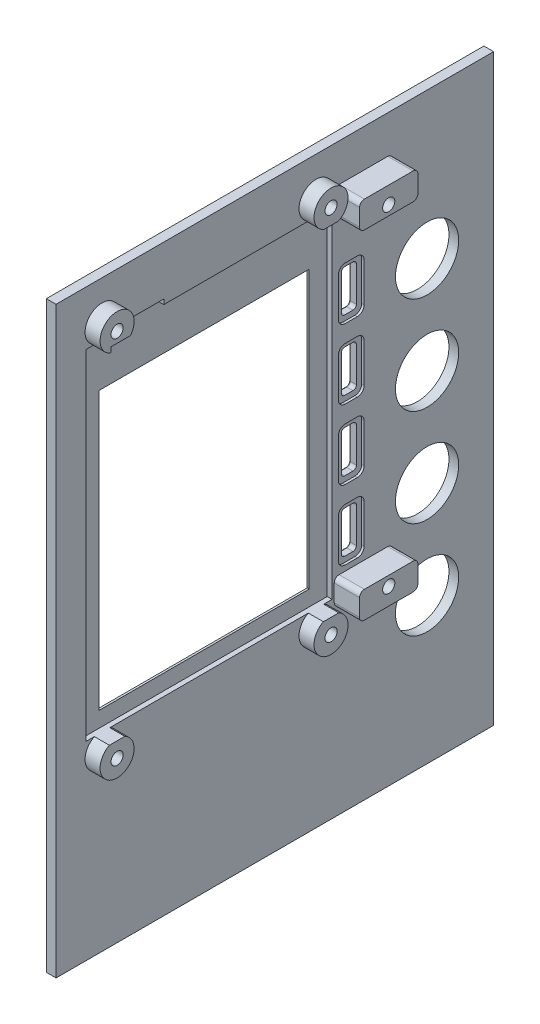
SolidWorks part; units mm, degrees
ref_plane "Front Plane" through (0, 0, 0) normal (0, 0, 1) x (1, 0, 0)
ref_plane "Top Plane" through (0, 0, 0) normal (0, 1, 0) x (1, 0, 0)
ref_plane "Right Plane" through (0, 0, 0) normal (1, 0, 0) x (0, 0, -1)
ref_plane "Plane2" through (-1175.0441, 0, 0) normal (-1, 0, 0) x (0, 0, 1)
sketch "Sketch2" plane through (-1175.0441, 0, 0) normal (-1, 0, 0) x (0, 0, 1)
  line L0 (-1293.9703, -887.0459) -> (-1293.9703, -787.0459) construction
  line L1 (-1208.9703, -777.0459) -> (-1298.9703, -777.0459)
  line L2 (-1208.9703, -777.0459) -> (-1208.9703, -897.0459)
  line L3 (-1208.9703, -897.0459) -> (-1298.9703, -897.0459)
  line L4 (-1298.9703, -777.0459) -> (-1298.9703, -897.0459)
  line L5 (-1293.9703, -887.0459) -> (-1292.4603, -887.0459) construction
  line L6 (-1293.9703, -787.0459) -> (-1292.4603, -787.0459) construction
  circle A0 centre (-1285.2753, -867.0459) radius 6.5
  circle A1 centre (-1285.2753, -847.0459) radius 6.5
  circle A2 centre (-1285.2753, -827.0459) radius 6.5
  circle A3 centre (-1285.2753, -807.0459) radius 6.5
  ellipse E0 centre (-1285.2753, -867.0459) end of major axis (-1284.8157, -867.5055) minor radius 0.65 construction
  ellipse E1 centre (-1285.2753, -847.0459) end of major axis (-1284.8157, -847.5055) minor radius 0.65 construction
  ellipse E2 centre (-1285.2753, -827.0459) end of major axis (-1284.8157, -827.5055) minor radius 0.65 construction
  ellipse E3 centre (-1285.2753, -807.0459) end of major axis (-1284.8157, -807.5055) minor radius 0.65 construction
  ellipse E4 centre (-1285.2753, -867.0459) end of major axis (-1284.8157, -867.5055) minor radius 0.65
  ellipse E5 centre (-1285.2753, -847.0459) end of major axis (-1284.8157, -847.5055) minor radius 0.65 construction
  ellipse E6 centre (-1285.2753, -827.0459) end of major axis (-1284.8157, -827.5055) minor radius 0.65
  ellipse E7 centre (-1285.2753, -807.0459) end of major axis (-1284.8157, -807.5055) minor radius 0.65
  dimension "D5" = 13
  dimension "D6" = 13
  dimension "D7" = 13
  dimension "D8" = 13
  dimension "D1" = 5
  dimension "D2" = 10
  dimension "D3" = 10
  dimension "D4" = 90
extrude "Boss-Extrude2" add sketch "Sketch2" along normal blind 2 contours L1 L4 L3 L2 A3 A2 A1 A0 region at (-1175.0441, -837.0459, -1252.3518)
sketch "Sketch3" plane through (-1177.0441, 0, 0) normal (-1, 0, 0) x (0, 0, 1)
  line L12 (-1218.8332, -854.8056) -> (-1262.0332, -854.8056) construction
  line L13 (-1262.0332, -854.8056) -> (-1262.0332, -797.8256) construction
  line L14 (-1218.8332, -797.8256) -> (-1218.8332, -854.8056) construction
  line L15 (-1262.0332, -797.8256) -> (-1218.8332, -797.8256) construction
  line L16 (-1218.8332, -854.8056) -> (-1262.0332, -854.8056)
  line L17 (-1262.0332, -854.8056) -> (-1262.0332, -797.8256)
  line L18 (-1218.8332, -797.8256) -> (-1218.8332, -854.8056)
  line L19 (-1262.0332, -797.8256) -> (-1218.8332, -797.8256)
extrude "tft_cutout" cut sketch "Sketch3" against normal through all
sketch "tft_inset_cutout" plane through (-1175.0441, 0, 0) normal (1, 0, 0) x (0, 0, -1)
  line L4 (1215.6332, -788.6846) -> (1215.6332, -857.4846) construction
  line L5 (1265.2332, -788.6846) -> (1215.6332, -788.6846) construction
  line L12 (1265.2332, -857.4846) -> (1265.2332, -788.6846) construction
  line L17 (1215.6332, -857.4846) -> (1265.2332, -857.4846) construction
  line L18 (1265.2332, -857.4846) -> (1265.2332, -788.6846) construction
  line L19 (1215.6332, -857.4846) -> (1265.2332, -857.4846) construction
  line L20 (1215.6332, -788.6846) -> (1215.6332, -857.4846) construction
  line L21 (1265.2332, -788.6846) -> (1215.6332, -788.6846) construction
  line L22 (1265.7332, -788.1846) -> (1215.1332, -788.1846)
  line L26 (1217.1332, -788.6846) -> (1231.1332, -788.6846)
  line L27 (1217.1332, -788.6846) -> (1217.1332, -787.1846)
  line L28 (1217.1332, -787.1846) -> (1231.1332, -787.1846)
  line L29 (1231.1332, -788.6846) -> (1231.1332, -787.1846)
  line L30 (1215.1332, -788.1846) -> (1215.1332, -857.9846)
  line L31 (1215.1332, -857.9846) -> (1265.7332, -857.9846)
  line L32 (1265.7332, -857.9846) -> (1265.7332, -788.1846)
  line M40 (1262.0332, -854.8056) -> (1218.8332, -854.8056)
  line M41 (1218.8332, -854.8056) -> (1218.8332, -797.8256)
  line M42 (1218.8332, -797.8256) -> (1262.0332, -797.8256)
  line M43 (1262.0332, -797.8256) -> (1262.0332, -854.8056)
  dimension "D3" = 1.5
  dimension "D4" = 0.5
  dimension "D1" = 14
  dimension "D2" = 1.5
extrude "Cut-Extrude2" cut sketch "tft_inset_cutout" against normal up to surface (1 mm away) contours L18 | L31 L32 L22 L29 L26 L27 L30 M43 M40 M41 M42 | L26 L29 L22 L27 | L22 L29 L28 L27 region at (-1175.0441, -823.0846, -1264.8711) region at (-1175.0441, -788.4346, -1224.1332) region at (-1175.0441, -787.6846, -1224.1332)
chamfer "Chamfer2" distance 1 angle 30 4 edges at (-1177.0441, -826.3156, -1262.0332) (-1177.0441, -854.8056, -1240.4332) (-1177.0441, -826.3156, -1218.8332) (-1177.0441, -797.8256, -1240.4332) first distance on face at (-1177.0441, -826.3156, -1240.4332)
sketch "Sketch6" plane through (-1175.0441, 0, 0) normal (1, 0, 0) x (0, 0, -1)
  line L5 (1266.1832, -859.8139) -> (1278.1832, -859.8139)
  line L6 (1266.1832, -859.8139) -> (1266.1832, -854.3139)
  line L7 (1266.1832, -854.3139) -> (1278.1832, -854.3139)
  line L8 (1266.1832, -859.8139) -> (1278.1832, -859.8139)
  line L9 (1278.1832, -859.8139) -> (1278.1832, -784.8139)
  line L10 (1278.1832, -784.8139) -> (1266.1832, -784.8139)
  line L11 (1266.1832, -784.8139) -> (1266.1832, -859.8139)
  line L12 (1266.1832, -859.8139) -> (1278.1832, -859.8139) construction
  line L13 (1278.1832, -859.8139) -> (1278.1832, -784.8139) construction
  line L14 (1278.1832, -784.8139) -> (1266.1832, -784.8139) construction
  line L15 (1266.1832, -784.8139) -> (1266.1832, -859.8139) construction
  line L16 (1278.1832, -859.8139) -> (1278.1832, -854.3139)
  line L17 (1266.1832, -784.8139) -> (1278.1832, -784.8139)
  line L18 (1266.1832, -784.8139) -> (1266.1832, -790.3139)
  line L19 (1266.1832, -790.3139) -> (1278.1832, -790.3139)
  line L20 (1278.1832, -784.8139) -> (1278.1832, -790.3139)
  circle A0 centre (1272.1832, -856.3139) radius 1.25 construction
  circle A1 centre (1272.1832, -856.3139) radius 1.25 construction
  circle A2 centre (1272.1832, -856.3139) radius 1.25
  circle A3 centre (1272.1832, -788.3139) radius 1.25 construction
  circle A4 centre (1272.1832, -788.3139) radius 1.25 construction
  circle A5 centre (1272.1832, -788.3139) radius 1.25
  dimension "D2" = 2.5
  dimension "D4" = 2.5
  dimension "D3" = 2
  dimension "D5" = 2
extrude "menu_standoffs" add sketch "Sketch6" along normal up to surface (5.203 mm away)
fillet "Fillet1" radius 1 8 edges at (-1172.4426, -790.3139, -1266.1832) (-1172.4426, -790.3139, -1278.1832) (-1172.4426, -784.8139, -1278.1832) (-1172.4426, -784.8139, -1266.1832) (-1172.4426, -854.3139, -1278.1832) (-1172.4426, -854.3139, -1266.1832) (-1172.4426, -859.8139, -1266.1832) (-1172.4426, -859.8139, -1278.1832)
sketch "Sketch7" plane through (-1169.8411, 0, 0) normal (1, 0, 0) x (0, 0, -1)
  circle A0 centre (1272.1832, -856.3139) radius 1.25 construction
  circle A1 centre (1272.1832, -788.3139) radius 1.25 construction
  circle A2 centre (1272.1832, -856.3139) radius 1.25
  circle A3 centre (1272.1832, -788.3139) radius 1.25
extrude "menu_standoff_holes" [suppressed] cut sketch "Sketch7" against normal blind 5 contours A2
sketch "Sketch8" plane through (-1175.0441, 0, 0) normal (1, 0, 0) x (0, 0, -1)
  circle A0 centre (1218.4332, -861.1056) radius 1.55 construction
  circle A1 centre (1262.4332, -861.1056) radius 1.55 construction
  circle A2 centre (1262.4332, -785.0256) radius 1.55 construction
  circle A3 centre (1218.4332, -785.0258) radius 1.55 construction
  circle A4 centre (1218.4332, -861.1056) radius 1.55 construction
  circle A5 centre (1262.4332, -861.1056) radius 1.55 construction
  circle A6 centre (1262.4332, -785.0256) radius 1.55 construction
  circle A7 centre (1218.4332, -785.0258) radius 1.55 construction
  circle A8 centre (1218.4332, -785.0258) radius 3.5
  circle A9 centre (1262.4332, -785.0256) radius 3.5
  circle A10 centre (1262.4332, -861.1056) radius 3.5
  circle A11 centre (1218.4332, -861.1056) radius 3.5
  circle A12 centre (1218.4332, -785.0258) radius 1.25
  circle A13 centre (1218.4332, -861.1056) radius 1.25
  circle A14 centre (1262.4332, -861.1056) radius 1.25
  circle A15 centre (1262.4332, -785.0256) radius 1.25
  dimension "D2" = 2.5
  dimension "D1" = 7
extrude "TFT_standoffs" add sketch "Sketch8" along normal up to surface (3.09 mm away)
sketch "Sketch9" plane through (-1175.0441, 0, 0) normal (1, 0, 0) x (0, 0, -1)
  circle A0 centre (1218.4332, -785.0258) radius 1.25 construction
  circle A1 centre (1218.4332, -861.1056) radius 1.25 construction
  circle A2 centre (1262.4332, -861.1056) radius 1.25 construction
  circle A3 centre (1262.4332, -785.0256) radius 1.25 construction
  circle A4 centre (1218.4332, -785.0258) radius 1.25
  circle A5 centre (1218.4332, -861.1056) radius 1.25
  circle A6 centre (1262.4332, -861.1056) radius 1.25
  circle A7 centre (1262.4332, -785.0256) radius 1.25
extrude "TFT_standoff_holes" cut sketch "Sketch9" against normal offset from surface (1 mm away) 1 up to face at (-1177.0441, -826.3156, -1240.4332)
extrude "Cut-Extrude5" cut sketch "Sketch5<3>" along normal through all contours L31 L32 L22 L29 L26 L27 L30 M43 M40 M41 M42 | L22 L29 L28 L27 | L26 L29 L22 L27 region at (-1175.0441, -823.0846, -1264.8711) region at (-1175.0441, -788.4346, -1224.1332) region at (-1175.0441, -787.6846, -1224.1332)
sketch "Sketch5<3>" plane through (-1175.0441, 0, 0) normal (1, 0, 0) x (0, 0, -1) same geometry as "tft_inset_cutout"
sketch "Sketch10" plane through (-1175.0441, 0, 0) normal (1, 0, 0) x (0, 0, -1)
  line L0 (1271.9367, -800.8206) -> (1271.9367, -808.8206) construction
  line L1 (1270.9367, -809.8206) -> (1268.4367, -809.8206) construction
  line L2 (1267.4367, -808.8206) -> (1267.4367, -800.8206) construction
  line L3 (1268.4367, -799.8206) -> (1270.9367, -799.8206) construction
  line L4 (1271.9367, -800.8206) -> (1271.9367, -808.8206) construction
  line L5 (1270.9367, -809.8206) -> (1268.4367, -809.8206) construction
  line L6 (1267.4367, -808.8206) -> (1267.4367, -800.8206) construction
  line L7 (1268.4367, -799.8206) -> (1270.9367, -799.8206) construction
  line L8 (1272.3367, -800.8206) -> (1272.3367, -808.8206)
  line L9 (1270.9367, -810.2206) -> (1268.4367, -810.2206)
  line L10 (1267.0367, -808.8206) -> (1267.0367, -800.8206)
  line L11 (1268.4367, -799.4206) -> (1270.9367, -799.4206)
  line L12 (1272.3367, -815.1506) -> (1272.3367, -823.1506)
  line L13 (1270.9367, -824.5506) -> (1268.4367, -824.5506)
  line L14 (1267.0367, -823.1506) -> (1267.0367, -815.1506)
  line L15 (1268.4367, -813.7506) -> (1270.9367, -813.7506)
  line L16 (1271.9367, -815.1506) -> (1271.9367, -823.1506) construction
  line L17 (1270.9367, -824.1506) -> (1268.4367, -824.1506) construction
  line L18 (1267.4367, -823.1506) -> (1267.4367, -815.1506) construction
  line L19 (1268.4367, -814.1506) -> (1270.9367, -814.1506) construction
  line L20 (1272.3367, -829.4806) -> (1272.3367, -837.4806)
  line L21 (1270.9367, -838.8806) -> (1268.4367, -838.8806)
  line L22 (1267.0367, -837.4806) -> (1267.0367, -829.4806)
  line L23 (1268.4367, -828.0806) -> (1270.9367, -828.0806)
  line L24 (1271.9367, -829.4806) -> (1271.9367, -837.4806) construction
  line L25 (1270.9367, -838.4806) -> (1268.4367, -838.4806) construction
  line L26 (1267.4367, -837.4806) -> (1267.4367, -829.4806) construction
  line L27 (1268.4367, -828.4806) -> (1270.9367, -828.4806) construction
  line L28 (1272.3367, -843.8106) -> (1272.3367, -851.8106)
  line L29 (1270.9367, -853.2106) -> (1268.4367, -853.2106)
  line L30 (1267.0367, -851.8106) -> (1267.0367, -843.8106)
  line L31 (1268.4367, -842.4106) -> (1270.9367, -842.4106)
  line L32 (1271.9367, -843.8106) -> (1271.9367, -851.8106) construction
  line L33 (1270.9367, -852.8106) -> (1268.4367, -852.8106) construction
  line L34 (1267.4367, -851.8106) -> (1267.4367, -843.8106) construction
  line L35 (1268.4367, -842.8106) -> (1270.9367, -842.8106) construction
  arc A0 (1271.9367, -800.8206) -> (1270.9367, -799.8206) centre (1270.9367, -800.8206) ccw construction
  arc A1 (1270.9367, -809.8206) -> (1271.9367, -808.8206) centre (1270.9367, -808.8206) ccw construction
  arc A2 (1267.4367, -808.8206) -> (1268.4367, -809.8206) centre (1268.4367, -808.8206) ccw construction
  arc A3 (1268.4367, -799.8206) -> (1267.4367, -800.8206) centre (1268.4367, -800.8206) ccw construction
  arc A4 (1271.9367, -800.8206) -> (1270.9367, -799.8206) centre (1270.9367, -800.8206) ccw construction
  arc A5 (1270.9367, -809.8206) -> (1271.9367, -808.8206) centre (1270.9367, -808.8206) ccw construction
  arc A6 (1267.4367, -808.8206) -> (1268.4367, -809.8206) centre (1268.4367, -808.8206) ccw construction
  arc A7 (1268.4367, -799.8206) -> (1267.4367, -800.8206) centre (1268.4367, -800.8206) ccw construction
  arc A8 (1270.9367, -810.2206) -> (1272.3367, -808.8206) centre (1270.9367, -808.8206) ccw
  arc A9 (1267.0367, -808.8206) -> (1268.4367, -810.2206) centre (1268.4367, -808.8206) ccw
  arc A10 (1268.4367, -799.4206) -> (1267.0367, -800.8206) centre (1268.4367, -800.8206) ccw
  arc A11 (1272.3367, -800.8206) -> (1270.9367, -799.4206) centre (1270.9367, -800.8206) ccw
  arc A12 (1270.9367, -824.5506) -> (1272.3367, -823.1506) centre (1270.9367, -823.1506) ccw
  arc A13 (1267.0367, -823.1506) -> (1268.4367, -824.5506) centre (1268.4367, -823.1506) ccw
  arc A14 (1268.4367, -813.7506) -> (1267.0367, -815.1506) centre (1268.4367, -815.1506) ccw
  arc A15 (1272.3367, -815.1506) -> (1270.9367, -813.7506) centre (1270.9367, -815.1506) ccw
  arc A16 (1271.9367, -815.1506) -> (1270.9367, -814.1506) centre (1270.9367, -815.1506) ccw construction
  arc A17 (1270.9367, -824.1506) -> (1271.9367, -823.1506) centre (1270.9367, -823.1506) ccw construction
  arc A18 (1267.4367, -823.1506) -> (1268.4367, -824.1506) centre (1268.4367, -823.1506) ccw construction
  arc A19 (1268.4367, -814.1506) -> (1267.4367, -815.1506) centre (1268.4367, -815.1506) ccw construction
  arc A20 (1270.9367, -838.8806) -> (1272.3367, -837.4806) centre (1270.9367, -837.4806) ccw
  arc A21 (1267.0367, -837.4806) -> (1268.4367, -838.8806) centre (1268.4367, -837.4806) ccw
  arc A22 (1268.4367, -828.0806) -> (1267.0367, -829.4806) centre (1268.4367, -829.4806) ccw
  arc A23 (1272.3367, -829.4806) -> (1270.9367, -828.0806) centre (1270.9367, -829.4806) ccw
  arc A24 (1271.9367, -829.4806) -> (1270.9367, -828.4806) centre (1270.9367, -829.4806) ccw construction
  arc A25 (1270.9367, -838.4806) -> (1271.9367, -837.4806) centre (1270.9367, -837.4806) ccw construction
  arc A26 (1267.4367, -837.4806) -> (1268.4367, -838.4806) centre (1268.4367, -837.4806) ccw construction
  arc A27 (1268.4367, -828.4806) -> (1267.4367, -829.4806) centre (1268.4367, -829.4806) ccw construction
  arc A28 (1270.9367, -853.2106) -> (1272.3367, -851.8106) centre (1270.9367, -851.8106) ccw
  arc A29 (1267.0367, -851.8106) -> (1268.4367, -853.2106) centre (1268.4367, -851.8106) ccw
  arc A30 (1268.4367, -842.4106) -> (1267.0367, -843.8106) centre (1268.4367, -843.8106) ccw
  arc A31 (1272.3367, -843.8106) -> (1270.9367, -842.4106) centre (1270.9367, -843.8106) ccw
  arc A32 (1271.9367, -843.8106) -> (1270.9367, -842.8106) centre (1270.9367, -843.8106) ccw construction
  arc A33 (1270.9367, -852.8106) -> (1271.9367, -851.8106) centre (1270.9367, -851.8106) ccw construction
  arc A34 (1267.4367, -851.8106) -> (1268.4367, -852.8106) centre (1268.4367, -851.8106) ccw construction
  arc A35 (1268.4367, -842.8106) -> (1267.4367, -843.8106) centre (1268.4367, -843.8106) ccw construction
  dimension "D1" = 0.4
  dimension "D2" = 4
extrude "Cut-Extrude6" cut sketch "Sketch10" against normal offset from surface 1.5 and the other way through all up to face at (-1177.0441, -826.3156, -1240.4332)
sketch "Sketch11" plane through (-1177.0441, 0, 0) normal (-1, 0, 0) x (0, 0, 1)
  line L0 (-1270.5367, -808.8206) -> (-1268.8367, -808.8206) construction
  line L1 (-1270.9367, -801.2206) -> (-1270.9367, -808.4206) construction
  line L2 (-1270.5367, -800.8206) -> (-1268.8367, -800.8206) construction
  line L3 (-1268.4367, -801.2206) -> (-1268.4367, -808.4206) construction
  line L4 (-1270.5367, -808.8206) -> (-1268.8367, -808.8206) construction
  line L5 (-1270.9367, -801.2206) -> (-1270.9367, -808.4206) construction
  line L6 (-1270.5367, -800.8206) -> (-1268.8367, -800.8206) construction
  line L7 (-1268.4367, -801.2206) -> (-1268.4367, -808.4206) construction
  line L8 (-1268.1367, -801.2206) -> (-1268.1367, -808.4206)
  line L9 (-1270.5367, -809.1206) -> (-1268.8367, -809.1206)
  line L10 (-1271.2367, -801.2206) -> (-1271.2367, -808.4206)
  line L11 (-1270.5367, -800.5206) -> (-1268.8367, -800.5206)
  line L12 (-1268.1367, -815.5506) -> (-1268.1367, -822.7506)
  line L13 (-1270.5367, -823.4506) -> (-1268.8367, -823.4506)
  line L14 (-1271.2367, -815.5506) -> (-1271.2367, -822.7506)
  line L15 (-1270.5367, -814.8506) -> (-1268.8367, -814.8506)
  line L16 (-1270.5367, -823.1506) -> (-1268.8367, -823.1506) construction
  line L17 (-1270.9367, -815.5506) -> (-1270.9367, -822.7506) construction
  line L18 (-1270.5367, -815.1506) -> (-1268.8367, -815.1506) construction
  line L19 (-1268.4367, -815.5506) -> (-1268.4367, -822.7506) construction
  line L20 (-1268.1367, -829.8806) -> (-1268.1367, -837.0806)
  line L21 (-1270.5367, -837.7806) -> (-1268.8367, -837.7806)
  line L22 (-1271.2367, -829.8806) -> (-1271.2367, -837.0806)
  line L23 (-1270.5367, -829.1806) -> (-1268.8367, -829.1806)
  line L24 (-1270.5367, -837.4806) -> (-1268.8367, -837.4806) construction
  line L25 (-1270.9367, -829.8806) -> (-1270.9367, -837.0806) construction
  line L26 (-1270.5367, -829.4806) -> (-1268.8367, -829.4806) construction
  line L27 (-1268.4367, -829.8806) -> (-1268.4367, -837.0806) construction
  line L28 (-1268.1367, -844.2106) -> (-1268.1367, -851.4106)
  line L29 (-1270.5367, -852.1106) -> (-1268.8367, -852.1106)
  line L30 (-1271.2367, -844.2106) -> (-1271.2367, -851.4106)
  line L31 (-1270.5367, -843.5106) -> (-1268.8367, -843.5106)
  line L32 (-1270.5367, -851.8106) -> (-1268.8367, -851.8106) construction
  line L33 (-1270.9367, -844.2106) -> (-1270.9367, -851.4106) construction
  line L34 (-1270.5367, -843.8106) -> (-1268.8367, -843.8106) construction
  line L35 (-1268.4367, -844.2106) -> (-1268.4367, -851.4106) construction
  arc A0 (-1268.8367, -808.8206) -> (-1268.4367, -808.4206) centre (-1268.8367, -808.4206) ccw construction
  arc A1 (-1270.9367, -808.4206) -> (-1270.5367, -808.8206) centre (-1270.5367, -808.4206) ccw construction
  arc A2 (-1270.5367, -800.8206) -> (-1270.9367, -801.2206) centre (-1270.5367, -801.2206) ccw construction
  arc A3 (-1268.4367, -801.2206) -> (-1268.8367, -800.8206) centre (-1268.8367, -801.2206) ccw construction
  arc A4 (-1268.8367, -808.8206) -> (-1268.4367, -808.4206) centre (-1268.8367, -808.4206) ccw construction
  arc A5 (-1270.9367, -808.4206) -> (-1270.5367, -808.8206) centre (-1270.5367, -808.4206) ccw construction
  arc A6 (-1270.5367, -800.8206) -> (-1270.9367, -801.2206) centre (-1270.5367, -801.2206) ccw construction
  arc A7 (-1268.4367, -801.2206) -> (-1268.8367, -800.8206) centre (-1268.8367, -801.2206) ccw construction
  arc A8 (-1268.8367, -809.1206) -> (-1268.1367, -808.4206) centre (-1268.8367, -808.4206) ccw
  arc A9 (-1271.2367, -808.4206) -> (-1270.5367, -809.1206) centre (-1270.5367, -808.4206) ccw
  arc A10 (-1270.5367, -800.5206) -> (-1271.2367, -801.2206) centre (-1270.5367, -801.2206) ccw
  arc A11 (-1268.1367, -801.2206) -> (-1268.8367, -800.5206) centre (-1268.8367, -801.2206) ccw
  arc A12 (-1268.8367, -823.4506) -> (-1268.1367, -822.7506) centre (-1268.8367, -822.7506) ccw
  arc A13 (-1271.2367, -822.7506) -> (-1270.5367, -823.4506) centre (-1270.5367, -822.7506) ccw
  arc A14 (-1270.5367, -814.8506) -> (-1271.2367, -815.5506) centre (-1270.5367, -815.5506) ccw
  arc A15 (-1268.1367, -815.5506) -> (-1268.8367, -814.8506) centre (-1268.8367, -815.5506) ccw
  arc A16 (-1268.8367, -823.1506) -> (-1268.4367, -822.7506) centre (-1268.8367, -822.7506) ccw construction
  arc A17 (-1270.9367, -822.7506) -> (-1270.5367, -823.1506) centre (-1270.5367, -822.7506) ccw construction
  arc A18 (-1270.5367, -815.1506) -> (-1270.9367, -815.5506) centre (-1270.5367, -815.5506) ccw construction
  arc A19 (-1268.4367, -815.5506) -> (-1268.8367, -815.1506) centre (-1268.8367, -815.5506) ccw construction
  arc A20 (-1268.8367, -837.7806) -> (-1268.1367, -837.0806) centre (-1268.8367, -837.0806) ccw
  arc A21 (-1271.2367, -837.0806) -> (-1270.5367, -837.7806) centre (-1270.5367, -837.0806) ccw
  arc A22 (-1270.5367, -829.1806) -> (-1271.2367, -829.8806) centre (-1270.5367, -829.8806) ccw
  arc A23 (-1268.1367, -829.8806) -> (-1268.8367, -829.1806) centre (-1268.8367, -829.8806) ccw
  arc A24 (-1268.8367, -837.4806) -> (-1268.4367, -837.0806) centre (-1268.8367, -837.0806) ccw construction
  arc A25 (-1270.9367, -837.0806) -> (-1270.5367, -837.4806) centre (-1270.5367, -837.0806) ccw construction
  arc A26 (-1270.5367, -829.4806) -> (-1270.9367, -829.8806) centre (-1270.5367, -829.8806) ccw construction
  arc A27 (-1268.4367, -829.8806) -> (-1268.8367, -829.4806) centre (-1268.8367, -829.8806) ccw construction
  arc A28 (-1268.8367, -852.1106) -> (-1268.1367, -851.4106) centre (-1268.8367, -851.4106) ccw
  arc A29 (-1271.2367, -851.4106) -> (-1270.5367, -852.1106) centre (-1270.5367, -851.4106) ccw
  arc A30 (-1270.5367, -843.5106) -> (-1271.2367, -844.2106) centre (-1270.5367, -844.2106) ccw
  arc A31 (-1268.1367, -844.2106) -> (-1268.8367, -843.5106) centre (-1268.8367, -844.2106) ccw
  arc A32 (-1268.8367, -851.8106) -> (-1268.4367, -851.4106) centre (-1268.8367, -851.4106) ccw construction
  arc A33 (-1270.9367, -851.4106) -> (-1270.5367, -851.8106) centre (-1270.5367, -851.4106) ccw construction
  arc A34 (-1270.5367, -843.8106) -> (-1270.9367, -844.2106) centre (-1270.5367, -844.2106) ccw construction
  arc A35 (-1268.4367, -844.2106) -> (-1268.8367, -843.8106) centre (-1268.8367, -844.2106) ccw construction
  dimension "D1" = 0.3
  dimension "D2" = 4
extrude "Cut-Extrude7" cut sketch "Sketch11" against normal through all
fillet "Fillet2" radius 0.25 32 edges at (-1177.0441, -804.8206, -1268.1367) (-1177.0441, -808.9155, -1268.3418) (-1177.0441, -809.1206, -1269.6867) (-1177.0441, -808.9155, -1271.0317) (-1177.0441, -804.8206, -1271.2367) (-1177.0441, -800.7256, -1271.0317) (-1177.0441, -800.5206, -1269.6867) (-1177.0441, -823.4506, -1269.6867) (-1177.0441, -823.2455, -1271.0317) (-1177.0441, -819.1506, -1271.2367) (-1177.0441, -815.0556, -1271.0317) (-1177.0441, -814.8506, -1269.6867) (-1177.0441, -815.0556, -1268.3418) (-1177.0441, -819.1506, -1268.1367) (-1177.0441, -837.7806, -1269.6867) (-1177.0441, -837.5755, -1271.0317) (-1177.0441, -833.4806, -1271.2367) (-1177.0441, -829.3856, -1271.0317) (-1177.0441, -829.1806, -1269.6867) (-1177.0441, -829.3856, -1268.3418) (-1177.0441, -833.4806, -1268.1367) (-1177.0441, -847.8106, -1268.1367) (-1177.0441, -851.9055, -1268.3418) (-1177.0441, -852.1106, -1269.6867) (-1177.0441, -851.9055, -1271.0317) (-1177.0441, -847.8106, -1271.2367) (-1177.0441, -843.7156, -1271.0317) (-1177.0441, -843.5106, -1269.6867) (-1177.0441, -800.7256, -1268.3418) (-1177.0441, -823.2455, -1268.3418) (-1177.0441, -837.5755, -1268.3418) (-1177.0441, -843.7156, -1268.3418)
equation "\"R_BNC\"= 13"
equation "\"D8@Sketch2\"=\"R_BNC\""
equation "\"D7@Sketch2\"=\"R_BNC\""
equation "\"D6@Sketch2\"=\"R_BNC\""
equation "\"D5@Sketch2\"=\"R_BNC\""
equation "\"R_m3_TAP\"= 2.5"
equation "\"D2@Sketch6\"=\"R_m3_TAP\""
equation "\"D4@Sketch6\"=\"R_m3_TAP\""
equation "\"R_TFT_mount_outer\" = 7"
equation "\"D1@Sketch8\"=\"R_TFT_mount_outer\""
equation "\"D2@Sketch8\"=\"R_m3_TAP\""
